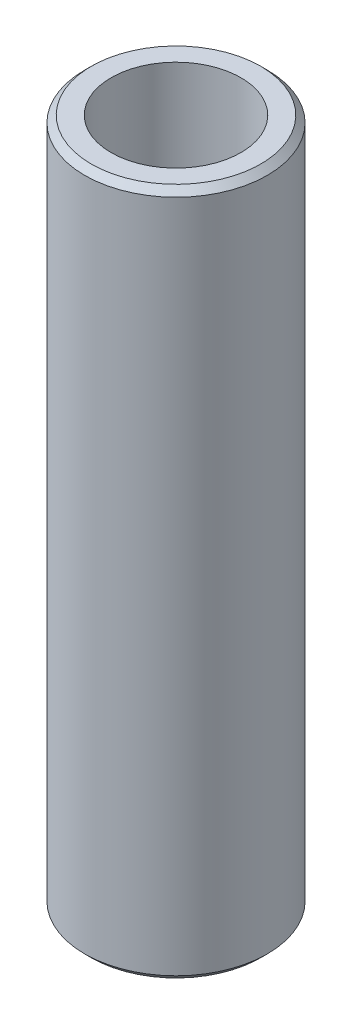
SolidWorks part; units mm, degrees
ref_plane "Front Plane" through (0, 0, 0) normal (0, 0, 1) x (1, 0, 0)
ref_plane "Top Plane" through (0, 0, 0) normal (0, 1, 0) x (1, 0, 0)
ref_plane "Right Plane" through (0, 0, 0) normal (1, 0, 0) x (0, 0, -1)
sketch "Sketch1" plane through (0, 0, 0) normal (0, 1, 0) x (1, 0, 0)
  circle A0 centre (0, 0) radius 20
  dimension "SHAFT_OD" = 40
extrude "Boss-Extrude1" add sketch "Sketch1" along normal blind 150.6045
sketch "Sketch2" plane through (0, 0, 0) normal (0, 1, 0) x (1, 0, 0)
  circle A0 centre (0, 0) radius 14.2219
  dimension "BORE_D" = 28.4439
extrude "Cut-Extrude1" cut sketch "Sketch2" along normal through all
chamfer "Chamfer1" distance 1.4365 angle 45 2 edges at (0, 150.6045, 20) (0, 0, 20)
